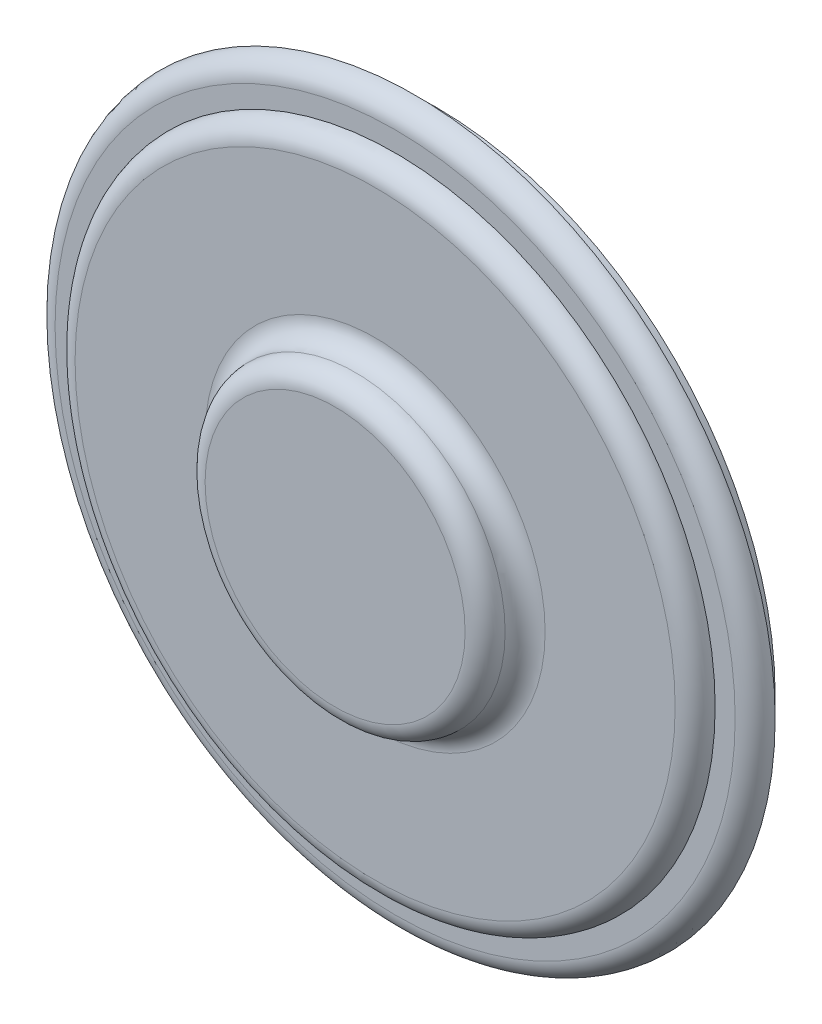
SolidWorks part; units mm, degrees
ref_plane "Front Plane" through (0, 0, 0) normal (0, 0, 1) x (1, 0, 0)
ref_plane "Top Plane" through (0, 0, 0) normal (0, 1, 0) x (1, 0, 0)
ref_plane "Right Plane" through (0, 0, 0) normal (1, 0, 0) x (0, 0, -1)
sketch "Sketch1" plane through (0, 0, 0) normal (0, 0, 1) x (1, 0, 0)
  circle A0 centre (0, 0) radius 18
  dimension "D1" = 36
other "Pen Sketch1" parameters "D1"=120.1356
extrude "Boss-Extrude1" add sketch "Sketch1" along normal blind 2
sketch "Sketch2" plane through (0, 0, 2) normal (0, 0, 1) x (1, 0, 0)
  circle A0 centre (0, 0) radius 16
  dimension "D1" = 32
extrude "Boss-Extrude2" add sketch "Sketch2" along normal blind 1
sketch "Sketch3" plane through (0, 0, 3) normal (0, 0, 1) x (1, 0, 0)
  circle A0 centre (0, 0) radius 7.5
  dimension "D1" = 15
extrude "Boss-Extrude3" add sketch "Sketch3" along normal blind 2
fillet "Fillet2" radius 1 4 edges at (16, 0, 3) (7.5, 0, 3) (7.5, 0, 5) (18, 0, 2)
sketch "Sketch4" plane through (0, 0, 0) normal (0, 0, -1) x (-1, 0, 0)
  circle A0 centre (0, 0) radius 18 construction
  circle A1 centre (0, 0) radius 18
  circle A2 centre (0, 0) radius 17
  dimension "D1" = 1
extrude "Cut-Extrude1" cut sketch "Sketch4" against normal blind 1
sketch "Sketch5" plane through (0, 0, 0) normal (0, 0, -1) x (-1, 0, 0)
  circle A0 centre (0, 0) radius 15.7895
  circle A1 centre (0, 0) radius 13.9322
extrude "Cut-Extrude2" cut sketch "Sketch5" against normal blind 1
sketch "Sketch6" plane through (0, 0, 0) normal (0, 0, -1) x (-1, 0, 0)
  circle A0 centre (0, 0) radius 3.891
  circle A1 centre (0, 0) radius 12.2316
extrude "Cut-Extrude3" cut sketch "Sketch6" against normal blind 1
fillet "Fillet3" radius 1 1 edges at (-3.891, 0, 0)
chamfer "Chamfer1" distance 1 angle 82 1 edges at (-12.2316, 0, 1) first distance on face at (-12.2316, 0, 1)
